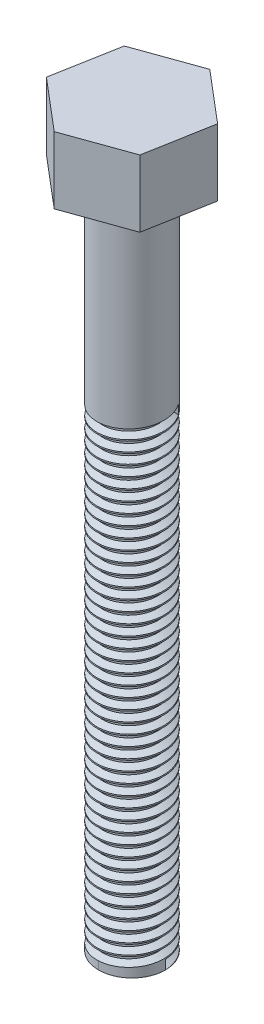
SolidWorks part; units mm, degrees
ref_plane "Front Plane" through (0, 0, 0) normal (0, 0, 1) x (1, 0, 0)
ref_plane "Top Plane" through (0, 0, 0) normal (0, 1, 0) x (1, 0, 0)
ref_plane "Right Plane" through (0, 0, 0) normal (1, 0, 0) x (0, 0, -1)
sketch "Sketch1" plane through (0, 0, 0) normal (0, 1, 0) x (1, 0, 0)
  line L1 (3.8158, -3.2311) -> (4.7061, 1.689)
  line L2 (4.7061, 1.689) -> (0.8903, 4.9201)
  line L3 (0.8903, 4.9201) -> (-3.8158, 3.2311)
  line L4 (-3.8158, 3.2311) -> (-4.7061, -1.689)
  line L5 (-4.7061, -1.689) -> (-0.8903, -4.9201)
  line L6 (-0.8903, -4.9201) -> (3.8158, -3.2311)
  circle A0 centre (0, 0) radius 5 construction
extrude "Boss-Extrude1" add sketch "Sketch1" along normal blind 5
sketch "Sketch2" plane through (0, 0, 0) normal (0, 1, 0) x (1, 0, 0)
  circle A0 centre (0, 0) radius 2.5
extrude "Boss-Extrude2" add sketch "Sketch2" against normal blind 50
thread "Thread1" pitch 0.7937 method cut profile "Thread Profile1" start angle 0, offset 0, length 35, pitch 0.7937, diameter 5
ref_plane "Plane1" through (2.5, -50, 0) normal (0, 0, 1) x (1, 0, 0)
sketch "Thread Profile1" plane through (2.5, -50, 0) normal (0, 0, 1) x (1, 0, 0)
  line L0 (0, 0) -> (0, 0.7937) construction
  line L11 (0, 0) -> (0, 0.6945)
  line L12 (0, 0.6945) -> (-0.4296, 0.4465)
  line L13 (-0.4296, 0.4465) -> (-0.4296, 0.248)
  line L15 (-0.4296, 0.248) -> (0, 0)
  line L17 (-0.4296, 0.3473) -> (0, 0.3473) construction
  point P2 (0, 0)
  dimension "Pitch" = 0.7937
  dimension "Profile_Angle" = 60
  dimension "Profile_Land" = 0.1984
  dimension "Profile_Height" = 0.4296
